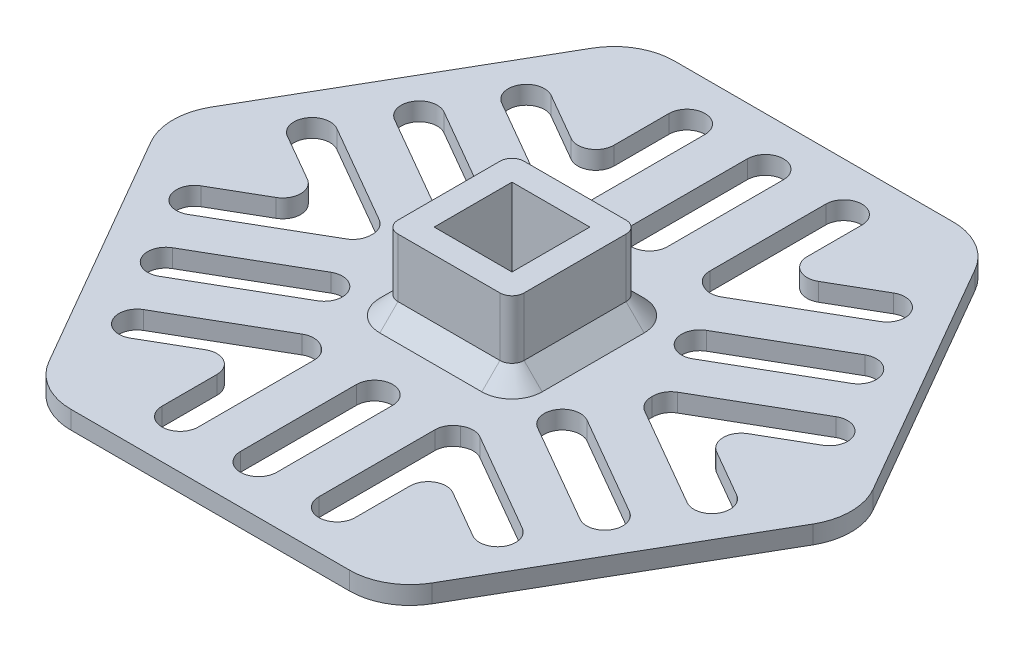
SolidWorks part; units mm, degrees
note: '?' marks a value the reader was unsure of.
ref_plane "Front Plane" through (0, 0, 0) normal (0, 0, 1) x (1, 0, 0)
ref_plane "Top Plane" through (0, 0, 0) normal (0, 1, 0) x (1, 0, 0)
ref_plane "Right Plane" through (0, 0, 0) normal (1, 0, 0) x (0, 0, -1)
sketch "Sketch1" plane through (0, 0, 0) normal (0, 1, 0) x (1, 0, 0)
  line L0 (-10.45, 10.45) -> (10.45, 10.45)
  line L1 (-6.45, -6.45) -> (6.45, -6.45)
  line L2 (-6.45, -6.45) -> (-6.45, 6.45)
  line L3 (-6.45, 6.45) -> (6.45, 6.45)
  line L4 (6.45, -6.45) -> (6.45, 6.45)
  line L5 (-6.45, -6.45) -> (6.45, 6.45) construction
  line L6 (-6.45, 6.45) -> (6.45, -6.45) construction
  line L7 (10.45, -10.45) -> (10.45, 10.45)
  line L8 (-10.45, -10.45) -> (10.45, -10.45)
  line L9 (-10.45, -10.45) -> (-10.45, 10.45)
  point P0 (0, 0)
  dimension "D1" = 12.9
  dimension "D2" = 4
extrude "Boss-Extrude1" add sketch "Sketch1" against normal blind 12.7
sketch "Sketch2" plane through (0, -12.7, 0) normal (0, -1, 0) x (1, 0, 0)
  line L1 (57.735, 0) -> (28.8675, 50)
  line L2 (28.8675, 50) -> (-28.8675, 50)
  line L3 (-28.8675, 50) -> (-57.735, 0)
  line L4 (-57.735, 0) -> (-28.8675, -50)
  line L5 (-28.8675, -50) -> (28.8675, -50)
  line L6 (28.8675, -50) -> (57.735, 0)
  circle A0 centre (0, 0) radius 50 construction
  dimension "D1" = 100
extrude "Boss-Extrude2" add sketch "Sketch2" along normal blind 3
sketch "Sketch3" plane through (0, -12.7, 0) normal (0, 1, 0) x (1, 0, 0)
  line L0 (-43.3013, 25) -> (-36.3731, 21) construction
  line L1 (-57.735, 0) -> (-28.8675, 50) construction
  line L2 (-36.3731, 21) -> (-19.7268, 11.3893) construction
  line L3 (-34.8731, 23.5981) -> (-18.2268, 13.9873)
  line L4 (-37.8731, 18.4019) -> (-21.2268, 8.7912)
  line L5 (-36.3731, 21) -> (-30.85, 30.5663) construction
  circle A0 centre (0, 0) radius 14.7785 construction
  circle A1 centre (0, 0) radius 22.7785 construction
  arc A2 (-34.8731, 23.5981) -> (-37.8731, 18.4019) centre (-36.3731, 21) ccw
  arc A3 (-21.2268, 8.7912) -> (-18.2268, 13.9873) centre (-19.7268, 11.3893) ccw
  point P10 (-28.0499, 16.1946)
  dimension "D3" = 3
  dimension "D2" = 8
  dimension "D1" = 8
extrude "Cut-Extrude1" cut sketch "Sketch3" against normal through all
pattern_linear "LPattern1" count 2 spacing 13 along (-0.5, 0, 0.866) count 2 spacing 13 along (0.5, 0, -0.866) of "Cut-Extrude1"
ref_axis "Axis1" through (0, 0.785, 0) along (0, -1, 0)?
pattern_circular "CirPattern1" count 6 over 360 about axis through (0, 0, 0) along (0, 1, 0) of "Cut-Extrude1", "LPattern1"
fillet "Fillet1" radius 3 6 edges at (-16, -14.2, -27.7128) (-16, -14.2, 27.7128) (16, -14.2, 27.7128) (32, -14.2, 0) (16, -14.2, -27.7128) (-32, -14.2, 0)
fillet "Fillet2" radius 10 6 edges at (28.8675, -14.2, -50) (-28.8675, -14.2, -50) (-57.735, -14.2, 0) (-28.8675, -14.2, 50) (28.8675, -14.2, 50) (57.735, -14.2, 0)
fillet "Fillet3" radius 2 4 edges at (-10.45, -6.35, 10.45) (10.45, -6.35, 10.45) (10.45, -6.35, -10.45) (-10.45, -6.35, -10.45)
chamfer "Chamfer1" distance 3 angle 45 8 edges at (0, -12.7, 10.45) (9.8642, -12.7, 9.8642) (-9.8642, -12.7, 9.8642) (10.45, -12.7, 0) (-10.45, -12.7, 0) (9.8642, -12.7, -9.8642) (-9.8642, -12.7, -9.8642) (0, -12.7, -10.45)
equation "\"D2@Sketch3\"=\"D1@Sketch3\""
